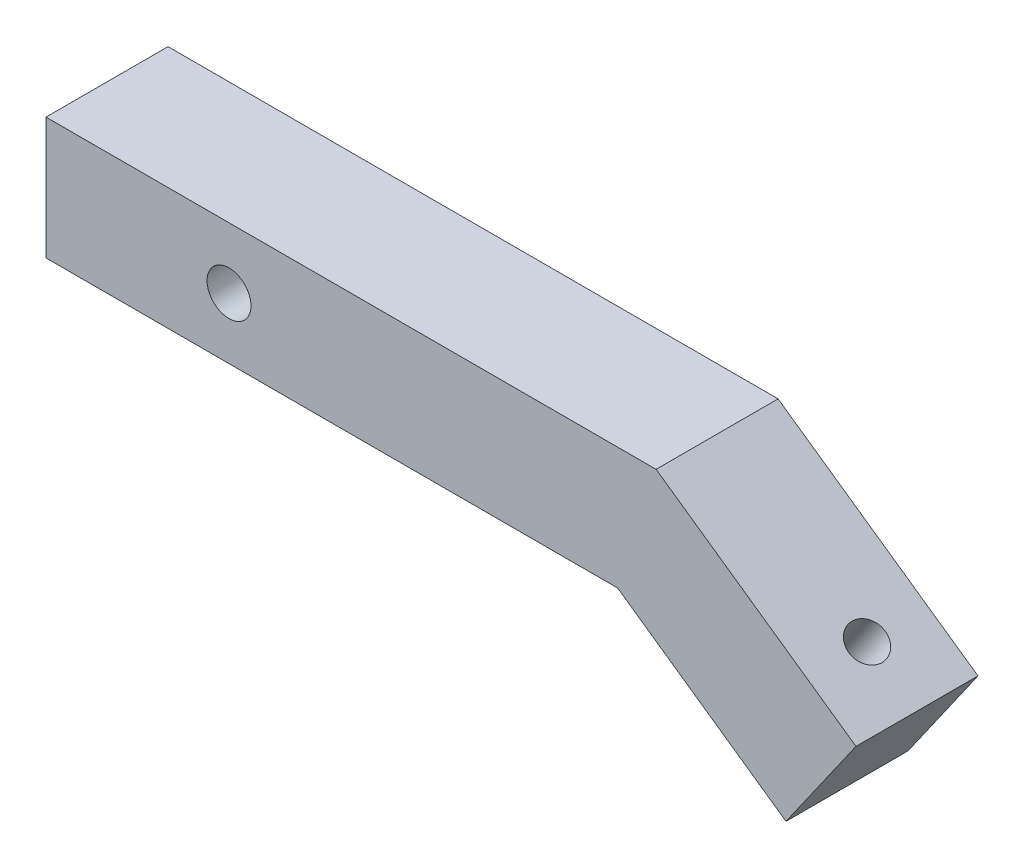
SolidWorks part; units mm, degrees
ref_plane "Front Plane" through (0, 0, 0) normal (0, 0, 1) x (1, 0, 0)
ref_plane "Top Plane" through (0, 0, 0) normal (0, 1, 0) x (1, 0, 0)
ref_plane "Right Plane" through (0, 0, 0) normal (1, 0, 0) x (0, 0, -1)
sketch "Sketch1" plane through (0, 0, 0) normal (0, 0, 1) x (1, 0, 0)
  line L0 (0, 0) -> (63.5, 0)
  line L1 (63.5, 0) -> (84.3065, -14.5688)
  line L2 (84.3065, -14.5688) -> (77.022, -24.9721)
  line L3 (77.022, -24.9721) -> (59.4957, -12.7)
  line L4 (59.4957, -12.7) -> (0, -12.7)
  line L5 (0, -12.7) -> (0, 0)
  point P3 (43.5342, -12.7)
  point P8 (50.7204, -12.7)
  dimension "D1" = 12.7
  dimension "D2" = 12.7
  dimension "D3" = 145
  dimension "D4" = 63.5
  dimension "D5" = 25.4
extrude "Boss-Extrude1" add sketch "Sketch1" along normal blind 12.7
sketch "Sketch2" plane through (0, 0, 0) normal (0, 0, -1) x (-1, 0, 0)
  line L0 (0, 0) -> (0, -12.7) construction
  line L1 (0, -12.7) -> (-59.4957, -12.7) construction
  circle A0 centre (-19.05, -6.35) radius 2.286
  dimension "D1" = 4.572
  dimension "D3" = 6.35
  dimension "D2" = 19.05
extrude "Cut-Extrude1" cut sketch "Sketch2" against normal blind 12.7
sketch "Sketch3" plane through (13.6064, 19.432, 0) normal (-0.5736, -0.8192, 0) x (0.8192, -0.5736, 0)
  line L0 (56.0204, 0) -> (77.4162, 0) construction
  line L1 (77.4162, 12.7) -> (77.4162, 0) construction
  circle A0 centre (71.0662, 6.35) radius 1.905
  dimension "D3" = 3.81
  dimension "D1" = 6.35
  dimension "D2" = 6.35
extrude "Cut-Extrude2" cut sketch "Sketch3" against normal blind 12.7
